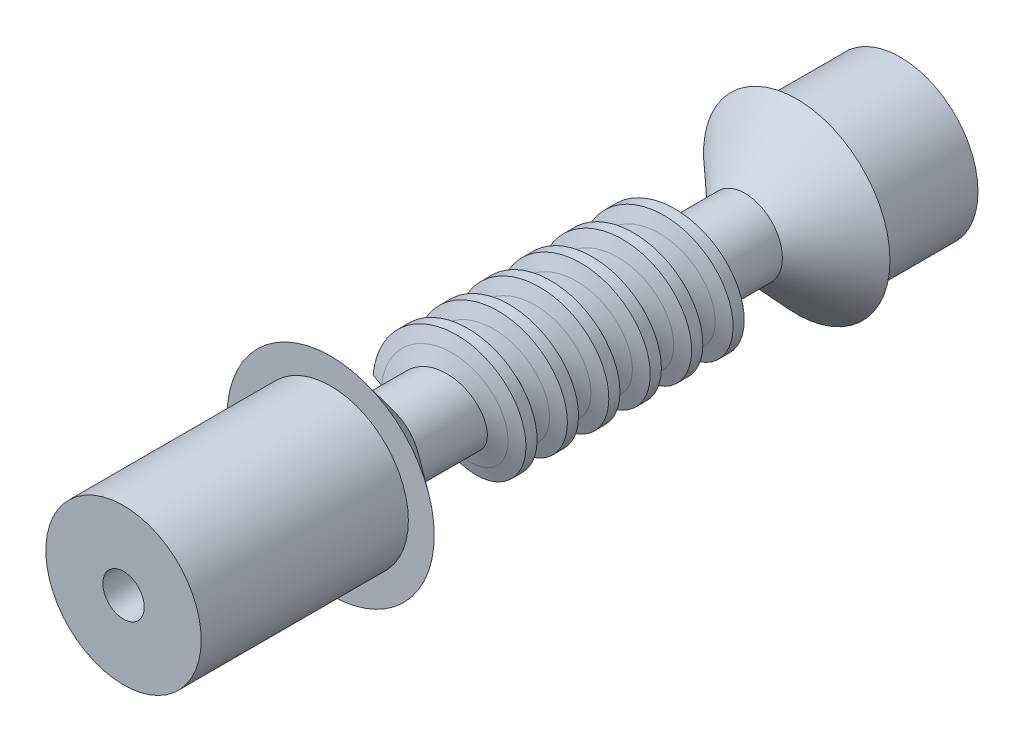
SolidWorks part; units mm, degrees
ref_plane "Front Plane" through (0, 0, 0) normal (0, 0, 1) x (1, 0, 0)
ref_plane "Top Plane" through (0, 0, 0) normal (0, 1, 0) x (1, 0, 0)
ref_plane "Right Plane" through (0, 0, 0) normal (1, 0, 0) x (0, 0, -1)
sketch "Sketch1" plane through (0, 0, 0) normal (0, 0, 1) x (1, 0, 0)
  circle A0 centre (0, 0) radius 3.61
  dimension "D1" = 7.22
extrude "Boss-Extrude1" add sketch "Sketch1" along normal blind 35
ref_plane "Plane2" through (0, 0, 5) normal (0, 0, -1) x (-1, 0, 0)
sketch "Sketch12" plane through (0, 0, 5) normal (0, 0, -1) x (-1, 0, 0)
  circle A0 centre (0, 0) radius 3.61
  dimension "D1" = 7.22
curve "Helix/Spiral4" pitch 4 height 24 radius 3.61 centre (0, 0, 5) axis (0, 0, 1) start towards (-1, 0, 0)
sketch "Sketch13" plane through (0, 0, 0) normal (0, 1, 0) x (1, 0, 0)
  line L0 (-6.36, -5.5378) -> (-6.36, -4.4622)
  line L1 (-5.09, -6) -> (-3.61, -6.5387)
  line L2 (-5.09, -4) -> (-6.36, -4.4622)
  line L4 (-5.09, -6) -> (-6.36, -5.5378)
  line L5 (-5.09, -4) -> (-3.61, -3.4613)
  line L6 (-3.61, -6.5387) -> (-3.61, -3.4613)
  point P2 (-6.36, -5)
  point P8 (-3.61, -5)
  point P9 (-3.61, -5)
sweep "Sweep4" add profiles "Sketch13" path "Helix/Spiral4"
sketch "Sketch23" plane through (0, 0, 0) normal (1, 0, 0) x (0, 0, -1)
  line L0 (-35, 0) -> (-40, 0) construction
  line L1 (-35, 3.61) -> (-35, -3.61) construction
  line L2 (-40, 0) -> (-40, 10)
  line L3 (-40, 10) -> (-35, 3.61)
  line L4 (-35, 3.61) -> (-35, 0)
  line L5 (-35, 0) -> (-40, 0)
revolve "Revolve1" add sketch "Sketch23" angle 360 about L0
sketch "Sketch24" plane through (0, 0, 40) normal (0, 0, 1) x (1, 0, 0)
  circle A0 centre (0, 0) radius 7.5
extrude "Boss-Extrude6" add sketch "Sketch24" along normal blind 10
sketch "Sketch25" plane through (0, 0, 50) normal (0, 0, 1) x (1, 0, 0)
  circle A0 centre (0, 0) radius 7.5
extrude "Boss-Extrude7" add sketch "Sketch25" along normal blind 10
sketch "Sketch26" plane through (0, 0, 0) normal (1, 0, 0) x (0, 0, -1)
  line L0 (0, 0) -> (5, 0) construction
  line L1 (5, 0) -> (5, 9)
  line L2 (5, 9) -> (0, 3.61)
  line L3 (0, -3.61) -> (0, 3.61) construction
  line L4 (0, 3.61) -> (0, 0)
  line L5 (0, 0) -> (5, 0)
revolve "Revolve2" add sketch "Sketch26" angle 360 about L0
sketch "Sketch27" plane through (0, 0, -5) normal (0, 0, -1) x (-1, 0, 0)
  circle A0 centre (0, 0) radius 7.5
extrude "Boss-Extrude8" add sketch "Sketch27" along normal blind 5
sketch "Sketch28" plane through (0, 0, -10) normal (0, 0, -1) x (-1, 0, 0)
  circle A0 centre (0, 0) radius 7.5
extrude "Boss-Extrude9" add sketch "Sketch28" along normal blind 5
sketch "Sketch29" plane through (0, 0, 60) normal (0, 0, 1) x (1, 0, 0)
  circle A0 centre (0, 0) radius 2
extrude "Cut-Extrude1" cut sketch "Sketch29" against normal blind 10
ref_plane "Plane3" through (0, 0, 18) normal (0, 0, 1) x (1, 0, 0)
sketch "Sketch31" plane through (0, 0, 18) normal (0, 0, 1) x (1, 0, 0)
  circle A0 centre (0, 0) radius 5.09
  dimension "D1" = 10.18
